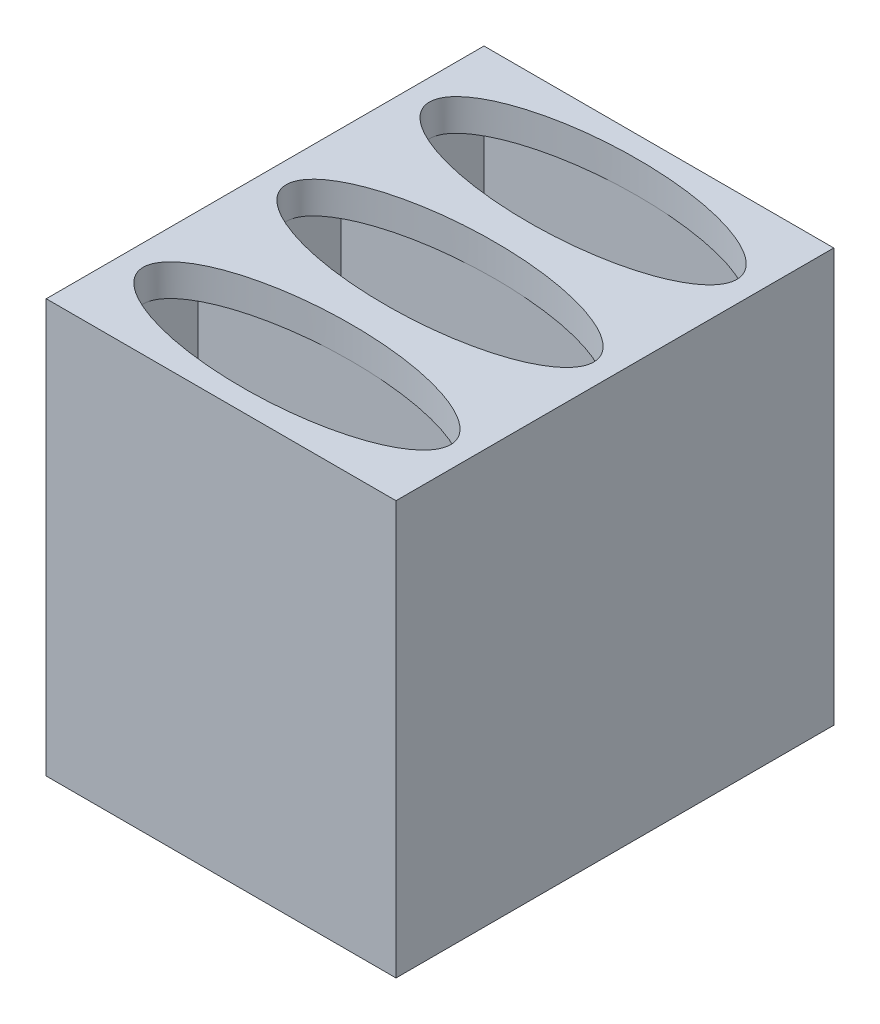
SolidWorks part; units mm, degrees
ref_plane "Front Plane" through (0, 0, 0) normal (0, 0, 1) x (1, 0, 0)
ref_plane "Top Plane" through (0, 0, 0) normal (0, 1, 0) x (1, 0, 0)
ref_plane "Right Plane" through (0, 0, 0) normal (1, 0, 0) x (0, 0, -1)
sketch "草图1" plane through (0, 0, 0) normal (0, 1, 0) x (1, 0, 0)
  line L0 (-16.5, -7.15) -> (-16.5, 7.15)
  line L1 (-14.5, -5.15) -> (14.5, -5.15)
  line L2 (-14.5, -5.15) -> (-14.5, 5.15)
  line L3 (-14.5, 5.15) -> (14.5, 5.15)
  line L4 (14.5, -5.15) -> (14.5, 5.15)
  line L5 (-14.5, -5.15) -> (14.5, 5.15) construction
  line L6 (-14.5, 5.15) -> (14.5, -5.15) construction
  line L7 (-16.5, 7.15) -> (16.5, 7.15)
  line L8 (16.5, -7.15) -> (16.5, 7.15)
  line L9 (-16.5, -7.15) -> (16.5, -7.15)
  point P0 (0, 0)
  dimension "D1" = 10.3
  dimension "D2" = 29
  dimension "D3" = 2
extrude "凸台-拉伸2" add sketch "草图1" along normal blind 36
sketch "草图2" plane through (0, 36, 0) normal (0, 1, 0) x (1, 0, 0)
  line L0 (14.5, -5.15) -> (14.5, 5.15) construction
  line L1 (16.5, 7.15) -> (-16.5, 7.15)
  line L2 (16.5, 7.15) -> (16.5, -7.15)
  line L3 (16.5, -7.15) -> (-16.5, -7.15)
  line L4 (-16.5, 7.15) -> (-16.5, -7.15)
  line L5 (-14.5, -5.15) -> (14.5, -5.15) construction
  ellipse E0 centre (0, 0) end of major axis (14.5, 0) minor radius 5.15
  point P7 (14.5, 0)
  point P16 (0, -3.8232)
  point P17 (0, -5.15)
extrude "凸台-拉伸3" add sketch "草图2" along normal blind 3
pattern_linear "阵列(线性)1" count 3 spacing 13.5 along (0, 0, 1) of "凸台-拉伸2", "凸台-拉伸3"
